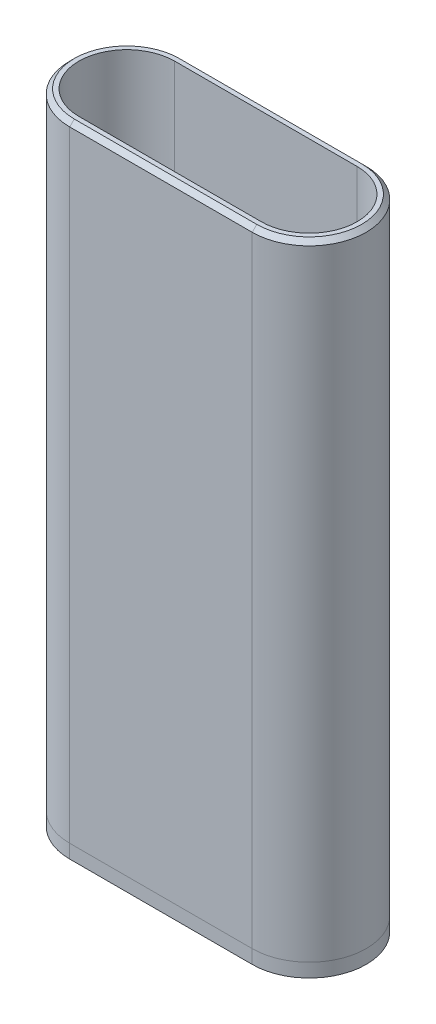
SolidWorks part; units mm, degrees
ref_plane "Front Plane" through (0, 0, 0) normal (0, 0, 1) x (1, 0, 0)
ref_plane "Top Plane" through (0, 0, 0) normal (0, 1, 0) x (1, 0, 0)
ref_plane "Right Plane" through (0, 0, 0) normal (1, 0, 0) x (0, 0, -1)
sketch "Sketch2" plane through (0, 12, 0) normal (0, -1, 0) x (1, 0, 0)
  line L8 (5.45, 3.45) -> (5.45, -3.45) construction
  line L9 (-7.45, -5.65) -> (7.45, -5.65)
  line L10 (-7.45, -5.65) -> (-7.45, 5.65)
  line L11 (-7.45, 5.65) -> (7.45, 5.65)
  line L12 (4.15, -3.65) -> (4.15, 3.65)
  line L13 (4.15, 3.65) -> (-4.15, 3.65)
  line L14 (-4.15, 3.65) -> (-4.15, -3.65)
  line L15 (-4.15, -3.65) -> (4.15, -3.65)
  line L16 (4.15, -3.65) -> (4.15, 3.65)
  line L17 (4.15, 3.65) -> (-4.15, 3.65)
  line L18 (-4.15, 3.65) -> (-4.15, -3.65)
  line L19 (-4.15, -3.65) -> (4.15, -3.65)
  line L20 (7.45, -5.65) -> (7.45, 5.65)
  line L21 (0, 5.65) -> (0, -5.65) construction
  line L22 (-7.45, 0) -> (7.45, 0) construction
  point P0 (0, 0)
  dimension "D2" = 2
  dimension "D3" = 2
  dimension "D4" = 8.3
  dimension "D5" = 7.3
  dimension "D1" = 0.2
extrude "Boss-Extrude1" add sketch "Sketch2" along normal offset from surface (12.6 mm away) 0.6 offset beyond the face yes
sketch "Sketch4" plane through (0, 0, 0) normal (1, 0, 0) x (0, 0, -1)
  line L1 (-1.6, 9.8) -> (-1.6, 8) construction
  line L2 (1.6, 8) -> (1.6, 9.8) construction
  line L3 (2.75, 8) -> (1.6, 8) construction
  line L4 (-1.6, 8) -> (-2.75, 8) construction
  line L5 (-2.75, 8) -> (-2.75, 12) construction
  line L6 (-2.75, 12) -> (-3.45, 12) construction
  line L7 (-3.45, 12) -> (-3.45, 0) construction
  line L8 (-3.45, 0) -> (3.45, 0) construction
  line L9 (3.45, 0) -> (3.45, 12) construction
  line L10 (3.45, 12) -> (2.75, 12) construction
  line L11 (2.75, 12) -> (2.75, 8) construction
  line L13 (-1.6, 9.8) -> (-1.6, 8) construction
  line L14 (1.6, 8) -> (1.6, 9.8) construction
  line L15 (2.75, 8) -> (1.6, 8) construction
  line L16 (-1.6, 8) -> (-2.75, 8) construction
  line L17 (-2.75, 8) -> (-2.75, 12) construction
  line L18 (-2.75, 12) -> (-3.45, 12) construction
  line L19 (-3.45, 12) -> (-3.45, 0) construction
  line L20 (-3.45, 0) -> (3.45, 0) construction
  line L21 (3.45, 0) -> (3.45, 12) construction
  line L22 (3.45, 12) -> (2.75, 12) construction
  line L23 (2.75, 12) -> (2.75, 8) construction
  line L24 (0, -990) -> (0, 49010) construction
  line L25 (-2.3, 10.1) -> (2.3, 10.1)
  line L26 (-2.3, 10.1) -> (-2.3, 7)
  line L27 (-2.3, 7) -> (2.3, 7)
  line L28 (1.6, 10) -> (-1.6, 10)
  line L29 (-1.6, 10) -> (-1.6, 9.8)
  line L30 (-1.6, 9.8) -> (1.6, 9.8)
  line L31 (1.6, 9.8) -> (1.6, 10)
  line L32 (1.6, 10) -> (-1.6, 10) construction
  line L33 (-1.6, 10) -> (-1.6, 9.8) construction
  line L34 (2.3, 10.1) -> (2.3, 7)
  line L35 (1.6, 9.8) -> (1.6, 10) construction
  point P20 (0, 10)
  dimension "D2" = 0.7
  dimension "D3" = 0.1
  dimension "D4" = 1
  dimension "D1" = 0
extrude "Cut-Extrude1" cut sketch "Sketch4" against normal through all both and the other way through all
sketch "Sketch5" plane through (0, -0.6, 0) normal (0, -1, 0) x (1, 0, 0)
  line L0 (-20, 0) -> (20, 0) construction
  line L1 (-20, 12.5) -> (20, 12.5)
  line L2 (-20, -12.5) -> (20, -12.5)
  arc A0 (-20, 12.5) -> (-20, -12.5) centre (-20, 0) ccw
  arc A1 (20, -12.5) -> (20, 12.5) centre (20, 0) ccw
  point P2 (0, 0)
  dimension "D1" = 25
  dimension "D2" = 40
extrude "Boss-Extrude2" add sketch "Sketch5" along normal blind 3
sketch "Sketch7" plane through (0, -0.6, 0) normal (0, 1, 0) x (1, 0, 0)
  line L0 (-20, -10.5) -> (20, -10.5)
  line L1 (20, 10.5) -> (-20, 10.5)
  line L2 (-20, -12.5) -> (20, -12.5)
  line L3 (20, 12.5) -> (-20, 12.5)
  line L4 (-20, -12.5) -> (20, -12.5)
  line L5 (20, 12.5) -> (-20, 12.5)
  arc A0 (20, -10.5) -> (20, 10.5) centre (20, 0) ccw
  arc A1 (-20, 10.5) -> (-20, -10.5) centre (-20, 0) ccw
  arc A2 (-20, 12.5) -> (-20, -12.5) centre (-20, 0) ccw
  arc A3 (20, -12.5) -> (20, 12.5) centre (20, 0) ccw
  arc A4 (-20, 12.5) -> (-20, -12.5) centre (-20, 0) ccw
  arc A5 (20, -12.5) -> (20, 12.5) centre (20, 0) ccw
  dimension "D1" = 0
  dimension "D2" = 2
extrude "Boss-Extrude3" add sketch "Sketch7" along normal blind 137 separate body
sketch "Sketch8" plane through (0, -0.6, 0) normal (0, -1, 0) x (1, 0, 0)
  line L0 (-7.45, -5.65) -> (7.45, -5.65) construction
  line L1 (-7.45, 5.65) -> (-7.45, -5.65) construction
  line L2 (7.45, 5.65) -> (-7.45, 5.65) construction
  line L3 (7.45, -5.65) -> (7.45, 5.65) construction
  line L4 (-7.45, -5.65) -> (7.45, -5.65) construction
  line L5 (-7.45, 5.65) -> (-7.45, -5.65) construction
  line L6 (7.45, 5.65) -> (-7.45, 5.65) construction
  line L7 (7.45, -5.65) -> (7.45, 5.65) construction
  line L12 (20, -12.5) -> (-20, -12.5) construction
  line L13 (-20, 12.5) -> (20, 12.5) construction
  line L14 (20, -12.5) -> (-20, -12.5)
  line L15 (-20, 12.5) -> (20, 12.5)
  line L17 (-14.45, 7.65) -> (14.45, 7.65)
  line L18 (-14.45, 7.65) -> (-14.45, -7.65)
  line L19 (-14.45, -7.65) -> (14.45, -7.65)
  line L20 (14.45, 7.65) -> (14.45, -7.65)
  arc A0 (20, -12.5) -> (20, 12.5) centre (20, 0) ccw construction
  arc A1 (-20, 12.5) -> (-20, -12.5) centre (-20, 0) ccw construction
  arc A2 (20, -12.5) -> (20, 12.5) centre (20, 0) ccw
  arc A3 (-20, 12.5) -> (-20, -12.5) centre (-20, 0) ccw
  dimension "D1" = 2
  dimension "D2" = 2
  dimension "D3" = 7
  dimension "D4" = 7
extrude "Boss-Extrude4" add sketch "Sketch8" against normal blind 7.2
sketch "Sketch9" plane through (0, -0.6, 0) normal (0, -1, 0) x (1, 0, 0)
  line L0 (-20, 0) -> (20, 0) construction
  point P4 (0, 0)
  dimension "D1" = 40
hole_wizard "M3 Clearance Hole1" positions "Sketch10" profile "Sketch11" hole size "M3" standard "ANSI Metric" end condition through all
sketch "Sketch10" plane through (0, -0.6, 0) normal (0, -1, 0) x (-1, 0, 0)
  point P0 (20, 0)
  point P3 (-20, 0)
sketch "Sketch11" plane through (-20, -0.6, 0) normal (1, 0, 0) x (0, 0, -1)
  line L0 (0, 0) -> (0, 137)
  line L1 (0, 137) -> (1.8, 137)
  line L2 (1.8, 137) -> (1.8, 0)
  line L5 (1.8, 0) -> (0, 0)
  line L11 (0, -6.35) -> (0, 107.95) construction
  dimension "Thru Hole Dia." = 3.6
  dimension "Thru Hole Depth" = 137
ref_plane "Plane1" through (0, 1.4, 0) normal (0, 1, 0) x (1, 0, 0)
sketch "Sketch13" plane through (0, 1.4, 0) normal (0, 1, 0) x (1, 0, 0)
  line L0 (-18.3546, 2.85) -> (-14.45, 2.85)
  line L1 (-18.3546, 2.85) -> (-21.6454, 2.85)
  line L2 (-21.6454, 2.85) -> (-23.2909, 0)
  line L3 (-23.2909, 0) -> (-21.6454, -2.85)
  line L4 (-21.6454, -2.85) -> (-18.3546, -2.85)
  line L5 (-18.3546, -2.85) -> (-16.7091, 0)
  line L6 (-16.7091, 0) -> (-18.3546, 2.85)
  line L13 (-14.45, -7.65) -> (-14.45, 7.65) construction
  line L14 (-14.45, 2.85) -> (-14.45, -2.85)
  line L15 (-14.45, -2.85) -> (-18.3546, -2.85)
  circle A0 centre (-20, 0) radius 2.85 construction
  dimension "D1" = 5.7
extrude "Cut-Extrude2" cut sketch "Sketch13" along normal blind 3 contours L15 L14 L0 L6 L5 | L5 L6 L1 L2 L3 L4 region at (-20, 1.4, 0) region at (-16.0275, 1.4, 0)
sketch "Sketch14" plane through (0, 4.4, 0) normal (0, -1, 0) x (1, 0, 0)
  line L0 (-14.45, 2.85) -> (-21.6454, 2.85) construction
  line L1 (-21.8, 2.85) -> (-18.2, 2.85)
  line L2 (-21.8, 2.85) -> (-21.8, -2.85)
  line L3 (-21.8, -2.85) -> (-18.2, -2.85)
  line L4 (-18.2, 2.85) -> (-18.2, -2.85)
  line L5 (-21.6454, -2.85) -> (-14.45, -2.85) construction
  line L6 (-21.8, 2.5823) -> (-21.6454, 2.85)
  line L7 (-23.2909, 0) -> (-21.6454, 2.85) construction
  line L8 (-21.8, -2.5823) -> (-21.6454, -2.85)
  line L9 (-21.6454, -2.85) -> (-23.2909, 0) construction
  circle A0 centre (-20, 0) radius 1.8 construction
  line M5 (-21.6454, -2.85) -> (-14.45, -2.85)
  line M7 (-14.45, 2.85) -> (-21.6454, 2.85)
  line M8 (-21.6454, 2.85) -> (-23.2909, 0)
  line M9 (-23.2909, 0) -> (-21.6454, -2.85)
  circle M10 centre (-20, 0) radius 1.8
extrude "Cut-Extrude3" cut sketch "Sketch14" against normal blind 0.3 contours L4 L2 M10 M9 M5 | L4 L2 M7 M8 M10 region at (-19.993, 4.4, 2.0729) region at (-19.993, 4.4, -2.0729)
sketch "Sketch15" plane through (0, 4.7, 0) normal (0, -1, 0) x (1, 0, 0)
  line L0 (-21.8, 2.5823) -> (-21.8, 0) construction
  line L1 (-18.2, -1.8) -> (-21.8, -1.8)
  line L2 (-18.2, -1.8) -> (-18.2, 1.8)
  line L3 (-18.2, 1.8) -> (-21.8, 1.8)
  line L4 (-21.8, -1.8) -> (-21.8, 1.8)
  line L5 (-18.2, 2.85) -> (-18.2, 0) construction
  arc A0 (-18.2, 0) -> (-21.8, 0) centre (-20, 0) ccw construction
  arc A1 (-21.8, 0) -> (-18.2, 0) centre (-20, 0) ccw construction
extrude "Cut-Extrude4" cut sketch "Sketch15" against normal blind 0.3
chamfer "Chamfer1" distance 1 angle 45 4 edges at (32.5, 136.4, 0) (0, 136.4, -12.5) (0, 136.4, 12.5) (-32.5, 136.4, 0)
mirror "Mirror1" about plane through (0, 0, 0) normal (1, 0, 0) of "Cut-Extrude4", "Cut-Extrude3", "Cut-Extrude2"
chamfer "Chamfer2" distance 1.5 angle 45 4 edges at (-14.45, -0.6, 0) (0, -0.6, 7.65) (14.45, -0.6, 0) (0, -0.6, -7.65)
equation "\"case_length\"= 140"
equation "\"plate_thickness\"= 3"
equation "\"D1@Boss-Extrude2\"=\"plate_thickness\""
equation "\"D1@Boss-Extrude3\"=\"case_length\"-\"plate_thickness\""
equation "\"case_height\"= 25"
equation "\"case_width\"= 65"
equation "\"case_to_shell_offset\"= 19.6"
equation "\"body_tip_distance\"= 30"
equation "\"D2@Sketch5\"=\"case_width\"-\"case_height\""
equation "\"D1@Sketch5\"=\"case_height\""
equation "\"D1@Sketch9\"= \"case_width\" - \"case_height\""
equation "\"D2@Sketch8\"=\"D1@Sketch8\""
equation "\"D4@Sketch8\"=\"D3@Sketch8\""
